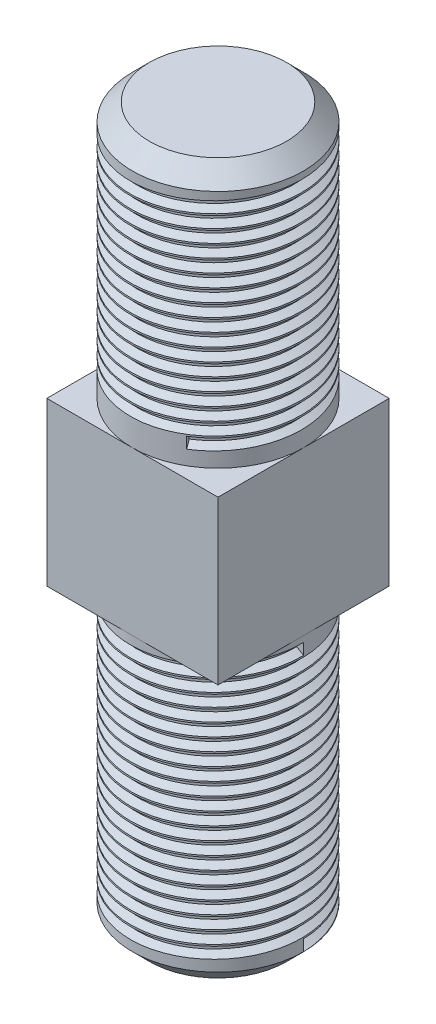
SolidWorks part; units mm, degrees
material "AISI 304"
ref_plane "Front Plane" through (0, 0, 0) normal (0, 0, 1) x (1, 0, 0)
ref_plane "Top Plane" through (0, 0, 0) normal (0, 1, 0) x (1, 0, 0)
ref_plane "Right Plane" through (0, 0, 0) normal (1, 0, 0) x (0, 0, -1)
sketch "Sketch2" plane through (0, 0, 0) normal (0, 1, 0) x (1, 0, 0)
  line L1 (-10, -10) -> (10, -10)
  line L2 (-10, -10) -> (-10, 10)
  line L3 (-10, 10) -> (10, 10)
  line L4 (10, -10) -> (10, 10)
  line L5 (-10, -10) -> (10, 10) construction
  line L6 (-10, 10) -> (10, -10) construction
  point P0 (0, 0)
  dimension "D1" = 20
  dimension "D2" = 20
extrude "Boss-Extrude1" add sketch "Sketch2" along normal blind 19
sketch "Sketch3" plane through (0, 19, 0) normal (0, 1, 0) x (1, 0, 0)
  circle A0 centre (0, 0) radius 10
  dimension "D1" = 20
extrude "Boss-Extrude2" add sketch "Sketch3" along normal blind 30
sketch "Sketch4" plane through (0, 0, 0) normal (0, -1, 0) x (1, 0, 0)
  circle A0 centre (0, 0) radius 10
  dimension "D1" = 20
extrude "Boss-Extrude3" add sketch "Sketch4" along normal blind 34
chamfer "Chamfer1" distance 2 angle 45 2 edges at (0, 49, 10) (0, -34, -10)
thread "Thread1" pitch 1.5 method cut profile "Thread Profile1" start angle 0, offset 0, length 25, pitch 1.5, diameter 20
ref_plane "Plane1" through (-10, 47, 0) normal (0, 0, 1) x (-1, 0, 0)
sketch "Thread Profile1" plane through (-10, 47, 0) normal (0, 0, 1) x (-1, 0, 0)
  line L0 (0, 0) -> (0, 1.5) construction
  line L11 (0, 0) -> (0, 1.3125)
  line L12 (0, 1.3125) -> (-0.8119, 0.8437)
  line L13 (-0.8119, 0.8437) -> (-0.8119, 0.4687)
  line L15 (-0.8119, 0.4687) -> (0, 0)
  line L17 (-0.8119, 0.6562) -> (0, 0.6562) construction
  point P2 (0, 0)
  dimension "Pitch" = 1.5
  dimension "Profile_Angle" = 60
  dimension "Profile_Land" = 0.375
  dimension "Profile_Height" = 0.8119
thread "Thread2" pitch 1.5 method cut profile "Thread Profile2" start angle 0, offset 0, length 30, pitch 1.5, diameter 20
ref_plane "Plane2" through (10, -32, 0) normal (0, 0, 1) x (1, 0, 0)
sketch "Thread Profile2" plane through (10, -32, 0) normal (0, 0, 1) x (1, 0, 0)
  line L0 (0, 0) -> (0, 1.5) construction
  line L11 (0, 0) -> (0, 1.3125)
  line L12 (0, 1.3125) -> (-0.8119, 0.8437)
  line L13 (-0.8119, 0.8437) -> (-0.8119, 0.4687)
  line L15 (-0.8119, 0.4687) -> (0, 0)
  line L17 (-0.8119, 0.6562) -> (0, 0.6562) construction
  point P2 (0, 0)
  dimension "Pitch" = 1.5
  dimension "Profile_Angle" = 60
  dimension "Profile_Land" = 0.375
  dimension "Profile_Height" = 0.8119
